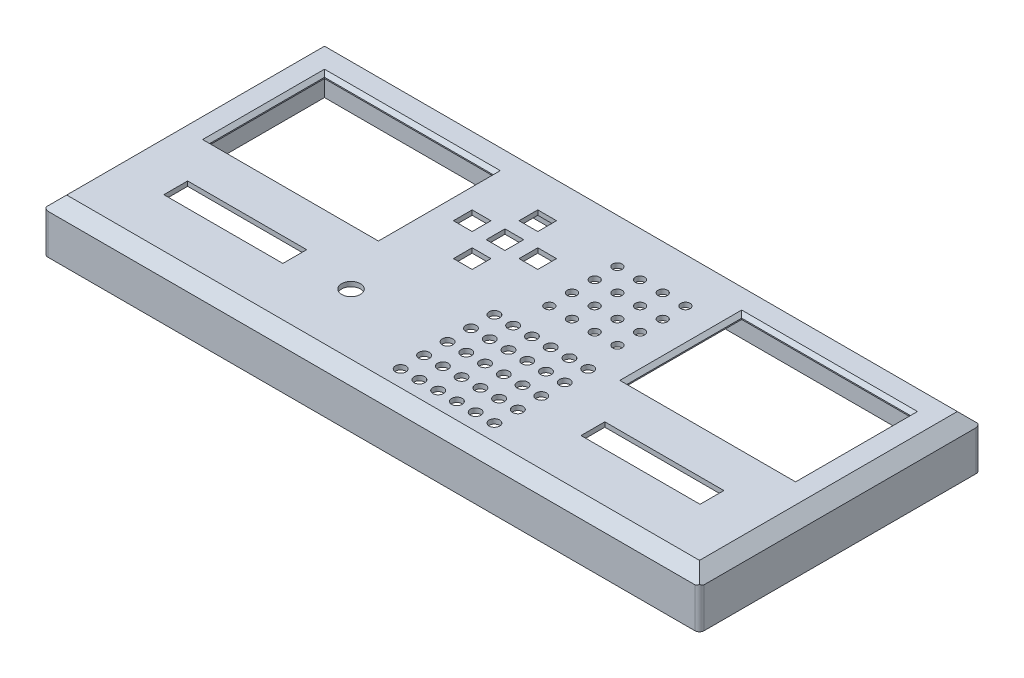
SolidWorks part; units mm, degrees
other "Markup1"
sketch "Sketch7" plane through (-140, 22, -60) normal (0, 1, 0) x (1, 0, 0)
ref_plane "Front Plane" through (0, 0, 0) normal (0, 0, 1) x (1, 0, 0)
ref_plane "Top Plane" through (0, 0, 0) normal (0, 1, 0) x (1, 0, 0)
ref_plane "Right Plane" through (0, 0, 0) normal (1, 0, 0) x (0, 0, -1)
sketch "Sketch1" plane through (0, 0, 0) normal (0, 1, 0) x (1, 0, 0)
  line L1 (-140, -60) -> (140, -60)
  line L2 (-140, -60) -> (-140, 60)
  line L3 (-140, 60) -> (140, 60)
  line L4 (140, -60) -> (140, 60)
  line L5 (-140, -60) -> (140, 60) construction
  line L6 (-140, 60) -> (140, -60) construction
  point P0 (0, 0)
  dimension "D1" = 280
  dimension "D2" = 120
extrude "Boss-Extrude1" add sketch "Sketch1" along normal blind 22
chamfer "Chamfer2" distance 5 angle 45 4 edges at (140, 22, 0) (0, 22, 60) (-140, 22, 0) (0, 22, -60)
fillet "Fillet1" radius 2 4 edges at (-140, 8.5, 60) (140, 8.5, 60) (140, 8.5, -60) (-140, 8.5, -60)
shell "Shell3" thickness 2 removed face at (0, 0, 0)
sketch "Sketch2" plane through (0, 22, 0) normal (0, 1, 0) x (1, 0, 0)
  line L0 (140, 60) -> (-140, 60) construction
  line L1 (-125, 45) -> (-53, 45)
  line L2 (-125, 45) -> (-125, -4)
  line L3 (-125, -4) -> (-53, -4)
  line L4 (-53, 45) -> (-53, -4)
  line L5 (-125, 45) -> (-53, -4) construction
  line L6 (-125, -4) -> (-53, 45) construction
  line L7 (-140, 60) -> (-140, -60) construction
  line L8 (0, -55) -> (0, 55) construction
  line L9 (125, -4) -> (53, -4)
  line L10 (53, 45) -> (53, -4)
  line L11 (125, 45) -> (53, 45)
  line L12 (125, 45) -> (125, -4)
  point P0 (-89, 20.5)
  dimension "D1" = 72
  dimension "D2" = 49
  dimension "D3" = 15
  dimension "D4" = 15
extrude "Cut-Extrude1" cut sketch "Sketch2" against normal blind 2
chamfer "Chamfer1" distance 1.5 angle 45 8 edges at (89, 22, 4) (53, 22, -20.5) (125, 22, -20.5) (89, 22, -45) (-125, 22, -20.5) (-89, 22, 4) (-53, 22, -20.5) (-89, 22, -45)
sketch "Sketch3" plane through (0, 22, 0) normal (0, 1, 0) x (1, 0, 0)
  line L0 (-138, 60) -> (138, 60) construction
  line L1 (53, 45) -> (53, -4) construction
  line L2 (-29, 18) -> (-29, 26)
  line L3 (-43, 18) -> (-35, 18)
  line L4 (-43, 18) -> (-43, 26)
  line L5 (-43, 26) -> (-35, 26)
  line L6 (-35, 18) -> (-35, 26)
  line L7 (-43, 18) -> (-35, 26) construction
  line L8 (-43, 26) -> (-35, 18) construction
  line L9 (-29, 18) -> (-21, 18)
  line L10 (-21, 18) -> (-21, 26)
  line L11 (-29, 26) -> (-21, 26)
  line L12 (-15, 18) -> (-15, 26)
  line L13 (-15, 18) -> (-7, 18)
  line L14 (-7, 18) -> (-7, 26)
  line L15 (-15, 26) -> (-7, 26)
  line L16 (-29, 32) -> (-29, 40)
  line L17 (-29, 40) -> (-21, 40)
  line L18 (-21, 32) -> (-21, 40)
  line L19 (-29, 32) -> (-21, 32)
  line L20 (-29, 4) -> (-29, 12)
  line L21 (-29, 12) -> (-21, 12)
  line L22 (-21, 4) -> (-21, 12)
  line L23 (-29, 4) -> (-21, 4)
  line L24 (-53, -4) -> (-53, 45) construction
  circle A0 centre (8.96, 36) radius 2
  circle A1 centre (18.64, 36) radius 2
  circle A2 centre (28.32, 36) radius 2
  circle A3 centre (38, 36) radius 2
  circle A4 centre (18.64, 26.32) radius 2
  circle A5 centre (28.32, 26.32) radius 2
  circle A6 centre (38, 26.32) radius 2
  circle A7 centre (18.64, 16.64) radius 2
  circle A8 centre (28.32, 16.64) radius 2
  circle A9 centre (38, 16.64) radius 2
  circle A10 centre (18.64, 6.96) radius 2
  circle A11 centre (28.32, 6.96) radius 2
  circle A12 centre (38, 6.96) radius 2
  circle A13 centre (8.96, 26.32) radius 2
  circle A14 centre (8.96, 16.64) radius 2
  circle A15 centre (8.96, 6.96) radius 2
  point P36 (-39, 22)
  point P55 (-43, 22)
  point P60 (0, 0)
  point P61 (0, 0)
  point P62 (0, 0)
  point P63 (0, 0)
  dimension "D1" = 4
  dimension "D4" = 24
  dimension "D5" = 15
  dimension "D6" = 8
  dimension "D10" = 6
  dimension "D11" = 6
  dimension "D12" = 10
  dimension "D13" = 20
  dimension "D14" = 6
  dimension "D2" = 4
  dimension "D3" = 4
  dimension "D7" = 3
  dimension "D8" = 2
  dimension "D9" = 2
extrude "Cut-Extrude2" cut sketch "Sketch3" against normal blind 2
sketch "Sketch4" plane through (0, 22, 0) normal (0, 1, 0) x (1, 0, 0)
  line L0 (-51.5, -5.5) -> (-126.5, -5.5) construction
  line L1 (-114.4, -24) -> (-63.6, -24)
  line L2 (-114.4, -24) -> (-114.4, -34.16)
  line L3 (-114.4, -34.16) -> (-63.6, -34.16)
  line L4 (-63.6, -24) -> (-63.6, -34.16)
  line L5 (-114.4, -24) -> (-63.6, -34.16) construction
  line L6 (-114.4, -34.16) -> (-63.6, -24) construction
  line L7 (-125, -4) -> (-53, -4) construction
  line L8 (0, -12.1) -> (0, 12.1) construction
  line L9 (114.4, -34.16) -> (63.6, -34.16)
  line L10 (63.6, -24) -> (63.6, -34.16)
  line L11 (114.4, -24) -> (63.6, -24)
  line L12 (114.4, -24) -> (114.4, -34.16)
  point P0 (-89, -29.08)
  point P7 (-89, -5.5)
  dimension "D1" = 50.8
  dimension "D2" = 10.16
  dimension "D3" = 20
extrude "Cut-Extrude3" cut sketch "Sketch4" against normal blind 2
sketch "Sketch6" plane through (0, 22, 0) normal (0, 1, 0) x (1, 0, 0)
  line L0 (138, -60) -> (-138, -60) construction
  line L1 (-51.5, 46.5) -> (-51.5, -5.5) construction
  circle A0 centre (0.5, -48) radius 2.25
  circle A1 centre (8.5, -48) radius 2.25
  circle A2 centre (16.5, -48) radius 2.25
  circle A3 centre (24.5, -48) radius 2.25
  circle A4 centre (32.5, -48) radius 2.25
  circle A5 centre (40.5, -48) radius 2.25
  circle A6 centre (8.5, -38) radius 2.25
  circle A7 centre (16.5, -38) radius 2.25
  circle A8 centre (24.5, -38) radius 2.25
  circle A9 centre (32.5, -38) radius 2.25
  circle A10 centre (40.5, -38) radius 2.25
  circle A11 centre (8.5, -28) radius 2.25
  circle A12 centre (16.5, -28) radius 2.25
  circle A13 centre (24.5, -28) radius 2.25
  circle A14 centre (32.5, -28) radius 2.25
  circle A15 centre (40.5, -28) radius 2.25
  circle A16 centre (8.5, -18) radius 2.25
  circle A17 centre (16.5, -18) radius 2.25
  circle A18 centre (24.5, -18) radius 2.25
  circle A19 centre (32.5, -18) radius 2.25
  circle A20 centre (40.5, -18) radius 2.25
  circle A21 centre (8.5, -8) radius 2.25
  circle A22 centre (16.5, -8) radius 2.25
  circle A23 centre (24.5, -8) radius 2.25
  circle A24 centre (32.5, -8) radius 2.25
  circle A25 centre (40.5, -8) radius 2.25
  circle A26 centre (0.5, -38) radius 2.25
  circle A27 centre (0.5, -28) radius 2.25
  circle A28 centre (0.5, -18) radius 2.25
  circle A29 centre (0.5, -8) radius 2.25
  dimension "D1" = 4.5
  dimension "D4" = 12
  dimension "D5" = 52
  dimension "D2" = 6
  dimension "D3" = 5
extrude "Cut-Extrude5" cut sketch "Sketch6" against normal blind 2
sketch "Sketch8" plane through (0, 22, 0) normal (0, 1, 0) x (1, 0, 0)
  line L0 (-63.6, -34.16) -> (-63.6, -24) construction
  line L1 (-63.6, -24) -> (-114.4, -24) construction
  circle A0 centre (-39.6, -29.08) radius 4
  dimension "D1" = 8
  dimension "D2" = 24
  dimension "D3" = 5.08
extrude "Cut-Extrude6" cut sketch "Sketch8" against normal blind 2
